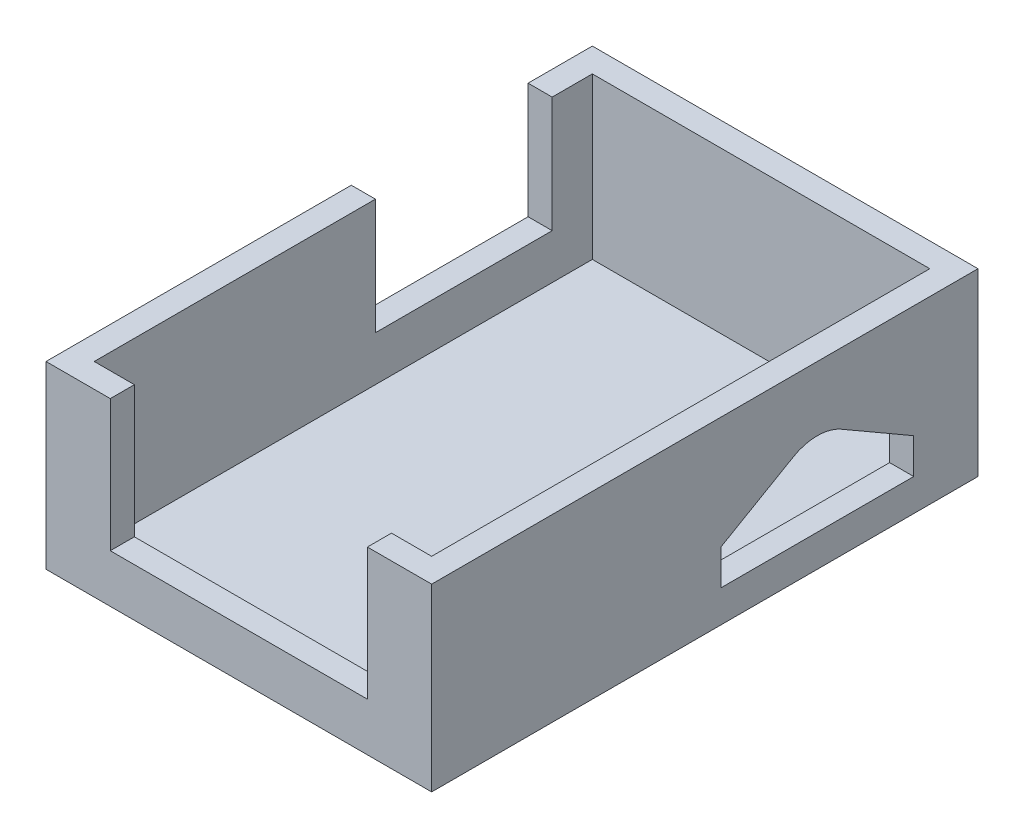
SolidWorks part; units mm, degrees
ref_plane "Płaszczyzna przednia" through (0, 0, 0) normal (0, 0, 1) x (1, 0, 0)
ref_plane "Płaszczyzna górna" through (0, 0, 0) normal (0, 1, 0) x (1, 0, 0)
ref_plane "Płaszczyzna prawa" through (0, 0, 0) normal (1, 0, 0) x (0, 0, -1)
sketch "Szkic1" plane through (0, 0, 0) normal (0, 1, 0) x (1, 0, 0)
  line L1 (-12, -17) -> (12, -17)
  line L2 (-12, -17) -> (-12, 17)
  line L3 (-12, 17) -> (12, 17)
  line L4 (12, -17) -> (12, 17)
  line L5 (-12, -17) -> (12, 17) construction
  line L6 (-12, 17) -> (12, -17) construction
  point P0 (0, 0)
  dimension "D1" = 24
  dimension "D2" = 34
extrude "Dodanie-wyciągnięcie1" add sketch "Szkic1" along normal blind 1.2
sketch "Szkic2" plane through (0, 1.2, 0) normal (0, 1, 0) x (1, 0, 0)
  line L0 (-12, 17) -> (12, 17)
  line L1 (12, 17) -> (12, -17)
  line L2 (12, -17) -> (-12, -17)
  line L3 (-12, -17) -> (-12, 17)
  line L5 (-10.5, -15.5) -> (10.5, -15.5)
  line L6 (-10.5, -15.5) -> (-10.5, 15.5)
  line L7 (-10.5, 15.5) -> (10.5, 15.5)
  line L8 (10.5, -15.5) -> (10.5, 15.5)
  line L9 (-10.5, -15.5) -> (10.5, 15.5) construction
  line L10 (-10.5, 15.5) -> (10.5, -15.5) construction
  point P4 (0, 0)
  dimension "D1" = 1.5
  dimension "D2" = 1.5
  dimension "D3" = 1.5
  dimension "D4" = 1.5
extrude "Dodanie-wyciągnięcie2" add sketch "Szkic2" along normal blind 10
sketch "Szkic3" plane through (12, 0, 0) normal (1, 0, 0) x (0, 0, -1)
  line L0 (17, 0) -> (17, 2) construction
  line L1 (17, 11.2) -> (17, 0) construction
  line L2 (17, 2) -> (13, 2) construction
  line L3 (13, 2) -> (1, 2)
  line L4 (1, 2) -> (1, 11.2)
  line L5 (-17, 11.2) -> (17, 11.2) construction
  line L6 (1, 11.2) -> (13, 11.2)
  line L7 (13, 11.2) -> (13, 2)
  dimension "D1" = 4
  dimension "D2" = 12
  dimension "D3" = 2
extrude "Wytnij-wyciągnięcie1" cut sketch "Szkic3" against normal up to surface (1.5 mm away) contours L3 L4 L6 L7 up to face at (10.5, 6.2, 0)
sketch "Szkic4" plane through (0, 0, 17) normal (0, 0, 1) x (1, 0, 0)
  line L0 (12, 0) -> (12, 3) construction
  line L1 (-12, 0) -> (12, 0) construction
  line L2 (12, 11.2) -> (12, 0) construction
  line L3 (12, 3) -> (8, 3) construction
  line L4 (8, 3) -> (8, 11.2)
  line L5 (-12, 11.2) -> (12, 11.2) construction
  line L6 (8, 11.2) -> (-8, 11.2)
  line L7 (-8, 11.2) -> (-8, 3)
  line L8 (-8, 3) -> (8, 3)
  line L9 (-12, 11.2) -> (-12, 0) construction
  dimension "D1" = 4
  dimension "D2" = 4
  dimension "D3" = 3
extrude "Wytnij-wyciągnięcie2" cut sketch "Szkic4" against normal up to surface (1.5 mm away) up to face at (0, 6.2, 15.5)
sketch "Szkic5" plane through (-12, 0, 0) normal (-1, 0, 0) x (0, 0, 1)
  line L0 (-17, 0) -> (-17, 4) construction
  line L1 (-17, 0) -> (17, 0) construction
  line L2 (-17, 11.2) -> (-17, 0) construction
  line L3 (-17, 4) -> (-13, 4) construction
  line L4 (-13, 4) -> (-13, 11.2)
  line L5 (-13, 11.2) -> (-2, 11.2)
  line L6 (-2, 11.2) -> (-2, 4)
  line L7 (-2, 4) -> (-13, 4)
  line L8 (-17, 11.2) -> (17, 11.2) construction
  dimension "D1" = 4
  dimension "D2" = 4
  dimension "D3" = 11
extrude "Wytnij-wyciągnięcie3" cut sketch "Szkic5" against normal up to surface (1.5 mm away) up to face at (-10.5, 6.2, 0)
sketch "Szkic6" plane through (12, 0, 0) normal (1, 0, 0) x (0, 0, -1)
  line L0 (13, 11.2) -> (1, 11.2)
  line L1 (13, 11.2) -> (17, 11.2) construction
  line L2 (13, 11.2) -> (13, 2) construction
  line L3 (1, 2) -> (1, 11.2) construction
  line L4 (-17, 11.2) -> (1, 11.2) construction
  line L5 (1, 11.2) -> (1, 4.2)
  line L6 (7, 11.2) -> (7, 7.6641) construction
  line L7 (7, 7.6641) -> (1, 4.2)
  line L8 (7, 7.6641) -> (13, 4.2)
  line L9 (13, 4.2) -> (13, 11.2)
  line L10 (1, 4.2) -> (13, 4.2) construction
  point P15 (13, 4.3394)
  dimension "D1" = 60
  dimension "D2" = 7
extrude "Dodanie-wyciągnięcie3" add sketch "Szkic6" against normal up to surface (1.5 mm away) up to face at (10.5, 6.4, -3.5)
fillet "Zaokrąglenie1" radius 3 1 edges at (11.25, 7.6641, -7)
